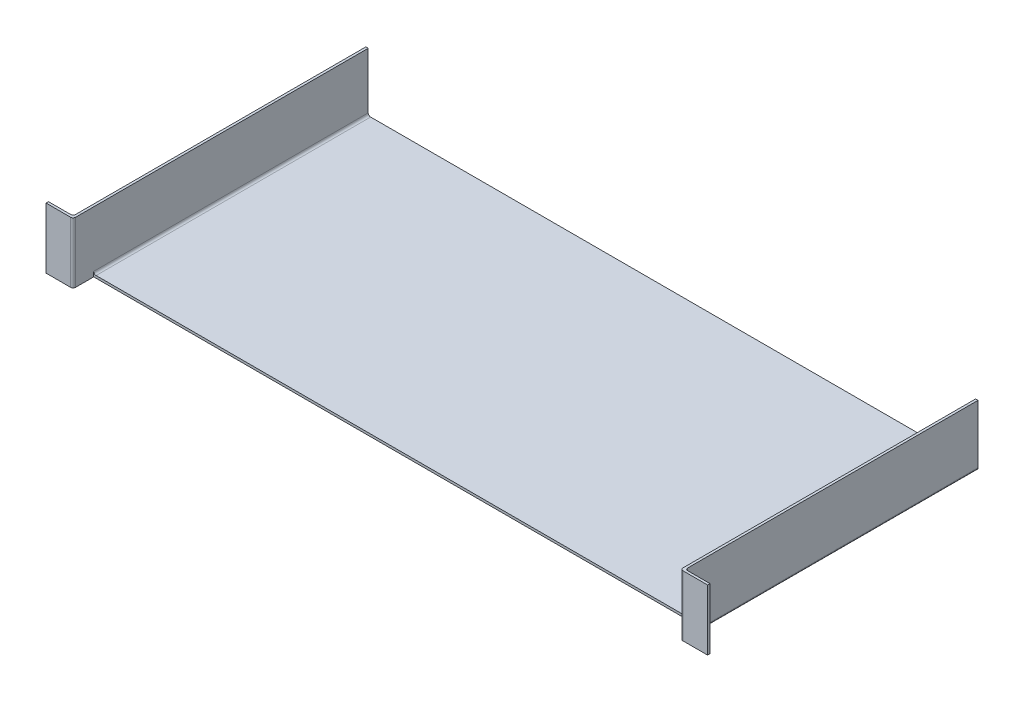
SolidWorks part; units mm, degrees
ref_plane "Front Plane" through (0, 0, 0) normal (0, 0, 1) x (1, 0, 0)
ref_plane "Top Plane" through (0, 0, 0) normal (0, 1, 0) x (1, 0, 0)
ref_plane "Right Plane" through (0, 0, 0) normal (1, 0, 0) x (0, 0, -1)
sketch "Sketch1" plane through (0, 0, 0) normal (0, 0, 1) x (1, 0, 0)
  line L0 (-221.25, 0) -> (221.25, 0)
  line L1 (221.25, 0) -> (221.25, 42.5)
  line L2 (221.25, 42.5) -> (-221.25, 42.5) construction
  line L3 (-221.25, 42.5) -> (-221.25, 0)
  line L4 (-221.25, 42.5) -> (-223, 42.5)
  line L5 (-223, 42.5) -> (-223, -1.75)
  line L6 (-223, -1.75) -> (223, -1.75)
  line L7 (223, -1.75) -> (223, 42.5)
  line L8 (223, 42.5) -> (221.25, 42.5)
  line L9 (-221.25, 0) -> (-221.25, -1.75) construction
  point P0 (0, 0)
  point P4 (0, 0)
  dimension "D1" = 446
  dimension "D2" = 1.75
  dimension "D3" = 44.25
extrude "Boss-Extrude1" add sketch "Sketch1" along normal blind 200
sketch "Sketch2" plane through (0, 0, 200) normal (0, 0, 1) x (1, 0, 0)
  line L1 (-223, -1.75) -> (-221.25, -1.75)
  line L2 (-223, -1.75) -> (-223, 42.5)
  line L3 (-223, 42.5) -> (-221.25, 42.5)
  line L4 (-221.25, -1.75) -> (-221.25, 42.5)
  line L5 (223, -1.75) -> (221.25, -1.75)
  line L6 (223, -1.75) -> (223, 42.5)
  line L7 (223, 42.5) -> (221.25, 42.5)
  line L8 (221.25, -1.75) -> (221.25, 42.5)
extrude "Boss-Extrude2" add sketch "Sketch2" along normal blind 15
sketch "Sketch3" plane through (223, 0, 0) normal (1, 0, 0) x (0, 0, -1)
  line L0 (-215, 42.5) -> (0, 42.5) construction
  line L1 (-215, -1.75) -> (-213.25, -1.75)
  line L2 (-215, -1.75) -> (-215, 42.5)
  line L3 (-215, 42.5) -> (-213.25, 42.5)
  line L4 (-213.25, -1.75) -> (-213.25, 42.5)
  dimension "D1" = 1.75
extrude "Boss-Extrude3" add sketch "Sketch3" along normal blind 18
sketch "Sketch4" plane through (-223, 0, 0) normal (-1, 0, 0) x (0, 0, 1)
  line L0 (215, 42.5) -> (0, 42.5) construction
  line L1 (215, -1.75) -> (213.25, -1.75)
  line L2 (215, -1.75) -> (215, 42.5)
  line L3 (215, 42.5) -> (213.25, 42.5)
  line L4 (213.25, -1.75) -> (213.25, 42.5)
  dimension "D1" = 1.75
extrude "Boss-Extrude4" add sketch "Sketch4" along normal blind 18
fillet "Fillet1" radius 1.75 8 edges at (-221.25, 0, 100) (-223, -1.75, 106.625) (223, -1.75, 106.625) (221.25, 0, 100) (223, 20.375, 213.25) (221.25, 20.375, 215) (-221.25, 20.375, 215) (-223, 20.375, 213.25) tangent propagation no
